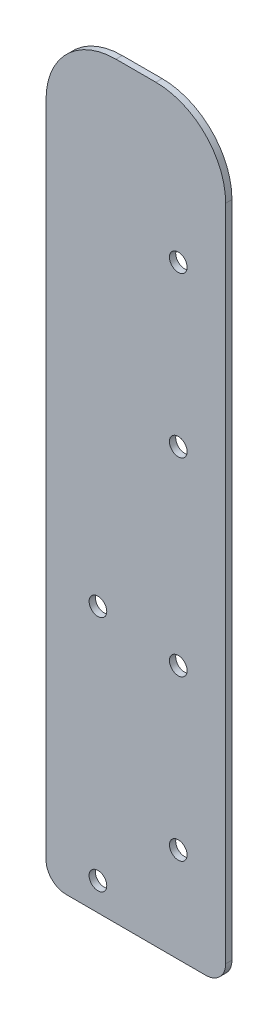
SolidWorks part; units mm, degrees
ref_plane "Front Plane" through (0, 0, 0) normal (0, 0, 1) x (1, 0, 0)
ref_plane "Top Plane" through (0, 0, 0) normal (0, 1, 0) x (1, 0, 0)
ref_plane "Right Plane" through (0, 0, 0) normal (1, 0, 0) x (0, 0, -1)
sketch "Sketch1" plane through (0, 0, 0) normal (0, 0, 1) x (1, 0, 0)
  line L1 (0, -146.6506) -> (0, 146.6506) construction
  line L3 (45.72, 5.08) -> (45.72, 172.72)
  line L5 (40.64, 0) -> (33.655, 0)
  line L7 (66.681, 0) -> (66.681, 88.9) construction
  line L8 (33.655, 0) -> (45.72, 0) construction
  line L9 (33.655, 177.8) -> (33.655, 0) construction
  line L10 (118.1346, 0) -> (-118.1346, 0) construction
  line L11 (66.681, 88.9) -> (0, 88.9) construction
  line L14 (33.655, 0) -> (5.07, 0.0545)
  line L18 (66.681, 88.9) -> (66.681, 177.8) construction
  line L19 (66.681, 177.8) -> (0, 177.8) construction
  line L20 (0, 5.08) -> (0, 172.72)
  line L23 (33.655, 0) -> (25.4, 0.0158) construction
  line L24 (13.208, 7.151) -> (13.208, 0.039) construction
  line L25 (25.4, 0.0158) -> (19.812, 0.0264) construction
  line L26 (19.812, 0.0264) -> (19.812, 8.89) construction
  line L27 (19.812, 8.89) -> (19.812, 177.8) construction
  line L28 (33.655, 24.13) -> (0, 24.13) construction
  line L35 (25.4, 0.0158) -> (22.7313, 0.0208) construction
  line L36 (66.681, 0) -> (0, 0) construction
  line L46 (17.78, 190.5) -> (27.94, 190.5)
  line L47 (19.9023, 177.8) -> (19.9023, 190.5) construction
  line L48 (20.4442, 160.274) -> (19.9023, 190.5) construction
  line L49 (19.9023, 190.5) -> (-14.4304, 190.5) construction
  line L50 (20.4442, 160.274) -> (0, 160.274) construction
  line L51 (45.72, 10.2129) -> (43.18, 10.2129) construction
  line L52 (43.18, 10.2129) -> (43.18, 0.6806) construction
  line L53 (43.18, 0.6806) -> (43.18, 181.8781) construction
  line L54 (13.208, 0.039) -> (13.208, 189.9021) construction
  circle A0 centre (33.655, 24.13) radius 2.2479
  circle A1 centre (33.655, 64.77) radius 2.2479
  arc A5 (40.64, 0) -> (45.72, 5.08) centre (40.64, 5.08) ccw
  arc A6 (5.07, 0.0545) -> (0, 5.08) centre (5.0797, 5.1345) cw
  circle A7 centre (33.655, 113.03) radius 2.2479
  circle A8 centre (33.655, 153.67) radius 2.2479
  arc A13 (45.72, 172.72) -> (27.94, 190.5) centre (27.94, 172.72) ccw
  arc A14 (0, 172.72) -> (17.78, 190.5) centre (17.78, 172.72) cw
  circle A15 centre (13.208, 7.151) radius 2.2479
  circle A17 centre (13.208, 67.6031) radius 2.2479
  point P24 (0, 190.5)
  point P30 (0, 0)
  point P38 (0, 190.5)
  point P42 (0, 185.42)
  point P46 (40.64, 185.0608)
  point P52 (0, 190.5)
  dimension "D7" = 4.4958
  dimension "D5" = 24.13
  dimension "D6" = 4.4958
  dimension "D9" = 24.13
  dimension "D11" = 88.9
  dimension "D12" = 5.08
  dimension "D13" = 4.4958
  dimension "D15" = 4.4958
  dimension "D17" = 4.4958
  dimension "D19" = 17.78
  dimension "D22" = 20.32
  dimension "D26" = 2.54
  dimension "D20" = 32.512
  dimension "D25" = 12.7
  dimension "D27" = 9.525
  dimension "D29" = 4.4958
  dimension "D1" = 190.5
  dimension "D2" = 45.72
  dimension "D3" = 88.9
  dimension "D4" = 9.525
  dimension "D8" = 40.64
  dimension "D10" = 24.13
  dimension "D14" = 7.112
  dimension "D16" = 40.64
  dimension "D18" = 24.13
  dimension "D21" = 30.226
  dimension "D28" = 64.77
  dimension "D30" = 67.564
extrude "Boss-Extrude2" add sketch "Sketch1" along normal blind 1.6002
